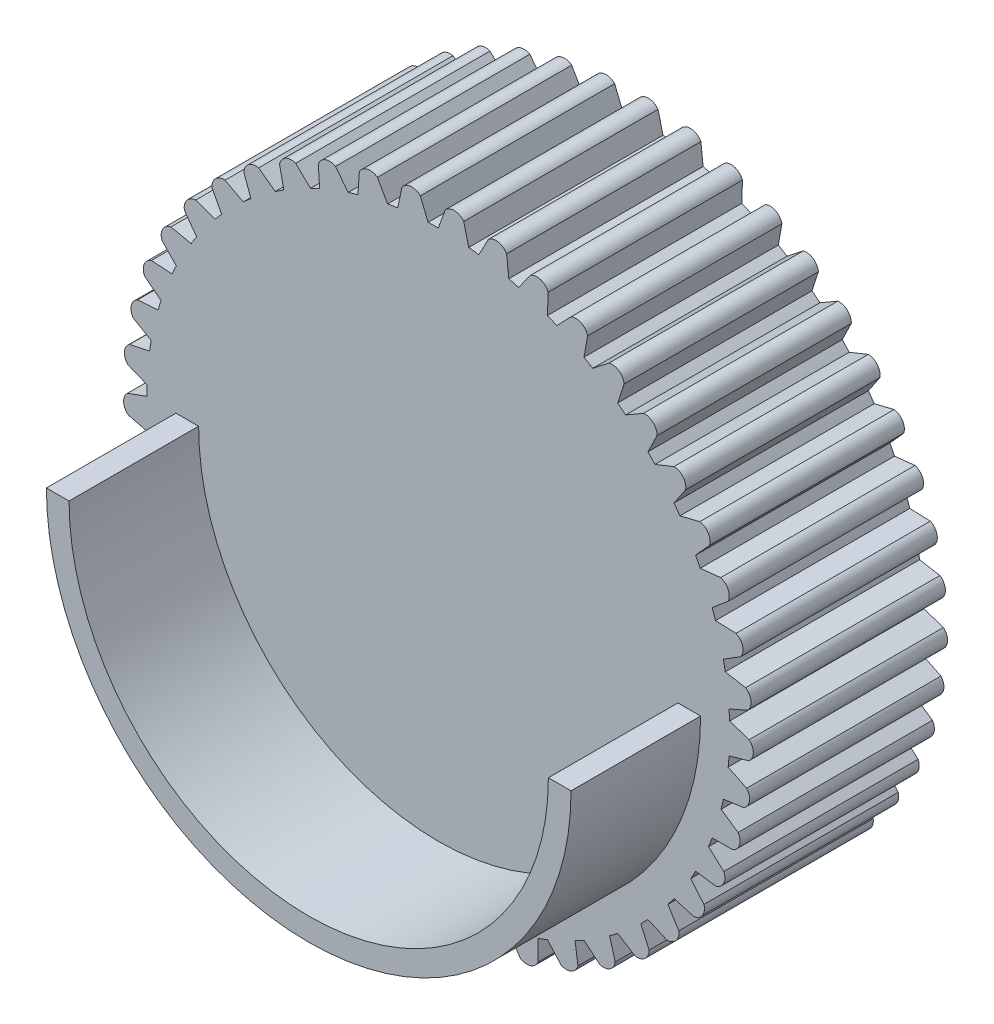
SolidWorks part; units mm, degrees
ref_plane "Front Plane" through (0, 0, 0) normal (0, 0, 1) x (1, 0, 0)
ref_plane "Top Plane" through (0, 0, 0) normal (0, 1, 0) x (1, 0, 0)
ref_plane "Right Plane" through (0, 0, 0) normal (1, 0, 0) x (0, 0, -1)
sketch "Sketch1" plane through (0, 0, 0) normal (0, 0, 1) x (1, 0, 0)
  circle A0 centre (0, 0) radius 22.5
  dimension "D1" = 45
extrude "Boss-Extrude1" add sketch "Sketch1" along normal blind 15
sketch "Sketch2" plane through (0, 0, 15) normal (0, 0, 1) x (1, 0, 0)
  circle A0 centre (0, 0) radius 20.25
  circle A1 centre (0, 0) radius 18.5
  dimension "D1" = 40.5
  dimension "D2" = 37
extrude "Boss-Extrude2" add sketch "Sketch2" along normal blind 10
sketch "Sketch3" plane through (0, 0, 15) normal (0, 0, 1) x (1, 0, 0)
  line L0 (0, 22.5) -> (0.5437, 23.9938)
  line L2 (2.3519, 22.3767) -> (1.9673, 23.9192)
  line L3 (0, 0) -> (0, 22.5)
  line L4 (2.3519, 22.3767) -> (0, 0)
  line L5 (0.5437, 23.9938) -> (1.9673, 23.9192)
  line L6 (0, 22.5) -> (0.5437, 23.9938)
  line L7 (1.9673, 23.9192) -> (2.3519, 22.3767)
  line L8 (3.1314, 22.281) -> (3.8777, 23.6847)
  line L9 (3.8777, 23.6847) -> (5.2771, 23.4127)
  line L10 (5.4432, 21.8317) -> (5.2771, 23.4127)
  line L11 (6.2018, 21.6284) -> (7.1362, 22.9145)
  line L12 (7.1362, 22.9145) -> (8.4841, 22.4504)
  line L13 (8.4286, 20.8616) -> (8.4841, 22.4504)
  line L14 (9.1516, 20.5548) -> (10.2559, 21.6983)
  line L15 (10.2559, 21.6983) -> (11.5261, 21.0511)
  line L16 (11.25, 19.4856) -> (11.5261, 21.0511)
  line L17 (11.9232, 19.0811) -> (13.1759, 20.0598)
  line L18 (13.1759, 20.0598) -> (14.3436, 19.2421)
  line L19 (13.8524, 17.7302) -> (14.3436, 19.2421)
  line L20 (14.4627, 17.236) -> (15.8395, 18.0309)
  line L21 (15.8395, 18.0309) -> (16.882, 17.0586)
  line L22 (16.1851, 15.6298) -> (16.882, 17.0586)
  line L23 (16.7208, 15.0554) -> (18.1947, 15.651)
  line L24 (18.1947, 15.651) -> (19.0918, 14.5431)
  line L25 (18.2029, 13.2252) -> (19.0918, 14.5431)
  line L26 (18.6533, 12.5818) -> (20.1958, 12.9664)
  line L27 (20.1958, 12.9664) -> (20.93, 11.7445)
  line L28 (19.8663, 10.5631) -> (20.93, 11.7445)
  line L29 (20.2229, 9.8634) -> (21.8039, 10.0295)
  line L30 (21.8039, 10.0295) -> (22.3609, 8.7173)
  line L31 (21.1431, 7.6955) -> (22.3609, 8.7173)
  line L32 (21.3988, 6.9529) -> (22.9875, 6.8974)
  line L33 (22.9875, 6.8974) -> (23.3565, 5.5204)
  line L34 (22.0083, 4.678) -> (23.3565, 5.5204)
  line L35 (22.1582, 3.9071) -> (23.7237, 3.631)
  line L36 (23.7237, 3.631) -> (23.8975, 2.2161)
  line L37 (22.4452, 1.5695) -> (23.8975, 2.2161)
  line L38 (22.4863, 0.7852) -> (23.9982, 0.294)
  line L39 (23.9982, 0.294) -> (23.9733, -1.1313)
  line L40 (22.4452, -1.5695) -> (23.9733, -1.1313)
  line L41 (22.3767, -2.3519) -> (23.8056, -3.0488)
  line L42 (23.8056, -3.0488) -> (23.5826, -4.4568)
  line L43 (22.0083, -4.678) -> (23.5826, -4.4568)
  line L44 (21.8317, -5.4432) -> (23.1496, -6.3322)
  line L45 (23.1496, -6.3322) -> (22.7328, -7.6955)
  line L46 (21.1431, -7.6955) -> (22.7328, -7.6955)
  line L47 (20.8616, -8.4286) -> (22.043, -9.4924)
  line L48 (22.043, -9.4924) -> (21.4406, -10.7844)
  line L49 (19.8663, -10.5631) -> (21.4406, -10.7844)
  line L50 (19.4856, -11.25) -> (20.5074, -12.4678)
  line L51 (20.5074, -12.4678) -> (19.731, -13.6634)
  line L52 (18.2029, -13.2252) -> (19.731, -13.6634)
  line L53 (17.7302, -13.8524) -> (18.5727, -15.2005)
  line L54 (18.5727, -15.2005) -> (17.6374, -16.2764)
  line L55 (16.1851, -15.6298) -> (17.6374, -16.2764)
  line L56 (15.6298, -16.1851) -> (16.2764, -17.6374)
  line L57 (16.2764, -17.6374) -> (15.2005, -18.5727)
  line L58 (13.8524, -17.7302) -> (15.2005, -18.5727)
  line L59 (13.2252, -18.2029) -> (13.6634, -19.731)
  line L60 (13.6634, -19.731) -> (12.4678, -20.5074)
  line L61 (11.25, -19.4856) -> (12.4678, -20.5074)
  line L62 (10.5631, -19.8663) -> (10.7844, -21.4406)
  line L63 (10.7844, -21.4406) -> (9.4924, -22.043)
  line L64 (8.4286, -20.8616) -> (9.4924, -22.043)
  line L65 (7.6955, -21.1431) -> (7.6955, -22.7328)
  line L66 (7.6955, -22.7328) -> (6.3322, -23.1496)
  line L67 (5.4432, -21.8317) -> (6.3322, -23.1496)
  line L68 (4.678, -22.0083) -> (4.4568, -23.5826)
  line L69 (4.4568, -23.5826) -> (3.0488, -23.8056)
  line L70 (2.3519, -22.3767) -> (3.0488, -23.8056)
  line L71 (1.5695, -22.4452) -> (1.1313, -23.9733)
  line L72 (1.1313, -23.9733) -> (-0.294, -23.9982)
  line L73 (-0.7852, -22.4863) -> (-0.294, -23.9982)
  line L74 (-1.5695, -22.4452) -> (-2.2161, -23.8975)
  line L75 (-2.2161, -23.8975) -> (-3.631, -23.7237)
  line L76 (-3.9071, -22.1582) -> (-3.631, -23.7237)
  line L77 (-4.678, -22.0083) -> (-5.5204, -23.3565)
  line L78 (-5.5204, -23.3565) -> (-6.8974, -22.9875)
  line L79 (-6.9529, -21.3988) -> (-6.8974, -22.9875)
  line L80 (-7.6955, -21.1431) -> (-8.7173, -22.3609)
  line L81 (-8.7173, -22.3609) -> (-10.0295, -21.8039)
  line L82 (-9.8634, -20.2229) -> (-10.0295, -21.8039)
  line L83 (-10.5631, -19.8663) -> (-11.7445, -20.93)
  line L84 (-11.7445, -20.93) -> (-12.9664, -20.1958)
  line L85 (-12.5818, -18.6533) -> (-12.9664, -20.1958)
  line L86 (-13.2252, -18.2029) -> (-14.5431, -19.0918)
  line L87 (-14.5431, -19.0918) -> (-15.651, -18.1947)
  line L88 (-15.0554, -16.7208) -> (-15.651, -18.1947)
  line L89 (-15.6298, -16.1851) -> (-17.0586, -16.882)
  line L90 (-17.0586, -16.882) -> (-18.0309, -15.8395)
  line L91 (-17.236, -14.4627) -> (-18.0309, -15.8395)
  line L92 (-17.7302, -13.8524) -> (-19.2421, -14.3436)
  line L93 (-19.2421, -14.3436) -> (-20.0598, -13.1759)
  line L94 (-19.0811, -11.9232) -> (-20.0598, -13.1759)
  line L95 (-19.4856, -11.25) -> (-21.0511, -11.5261)
  line L96 (-21.0511, -11.5261) -> (-21.6983, -10.2559)
  line L97 (-20.5548, -9.1516) -> (-21.6983, -10.2559)
  line L98 (-20.8616, -8.4286) -> (-22.4504, -8.4841)
  line L99 (-22.4504, -8.4841) -> (-22.9145, -7.1362)
  line L100 (-21.6284, -6.2018) -> (-22.9145, -7.1362)
  line L101 (-21.8317, -5.4432) -> (-23.4127, -5.2771)
  line L102 (-23.4127, -5.2771) -> (-23.6847, -3.8777)
  line L103 (-22.281, -3.1314) -> (-23.6847, -3.8777)
  line L104 (-22.3767, -2.3519) -> (-23.9192, -1.9673)
  line L105 (-23.9192, -1.9673) -> (-23.9938, -0.5437)
  line L106 (-22.5, 0) -> (-23.9938, -0.5437)
  line L107 (-22.4863, 0.7852) -> (-23.9602, 1.3808)
  line L108 (-23.9602, 1.3808) -> (-23.836, 2.8009)
  line L109 (-22.281, 3.1314) -> (-23.836, 2.8009)
  line L110 (-22.1582, 3.9071) -> (-23.5349, 4.7019)
  line L111 (-23.5349, 4.7019) -> (-23.2142, 6.0909)
  line L112 (-21.6284, 6.2018) -> (-23.2142, 6.0909)
  line L113 (-21.3988, 6.9529) -> (-22.6515, 7.9316)
  line L114 (-22.6515, 7.9316) -> (-22.1406, 9.2625)
  line L115 (-20.5548, 9.1516) -> (-22.1406, 9.2625)
  line L116 (-20.2229, 9.8634) -> (-21.3272, 11.0069)
  line L117 (-21.3272, 11.0069) -> (-20.6361, 12.2537)
  line L118 (-19.0811, 11.9232) -> (-20.6361, 12.2537)
  line L119 (-18.6533, 12.5818) -> (-19.5878, 13.8679)
  line L120 (-19.5878, 13.8679) -> (-18.7298, 15.0064)
  line L121 (-17.236, 14.4627) -> (-18.7298, 15.0064)
  line L122 (-16.7208, 15.0554) -> (-17.4671, 16.4591)
  line L123 (-17.4671, 16.4591) -> (-16.4591, 17.4671)
  line L124 (-15.0554, 16.7208) -> (-16.4591, 17.4671)
  line L125 (-14.4627, 17.236) -> (-15.0064, 18.7298)
  line L126 (-15.0064, 18.7298) -> (-13.8679, 19.5878)
  line L127 (-12.5818, 18.6533) -> (-13.8679, 19.5878)
  line L128 (-11.9232, 19.0811) -> (-12.2537, 20.6361)
  line L129 (-12.2537, 20.6361) -> (-11.0069, 21.3272)
  line L130 (-9.8634, 20.2229) -> (-11.0069, 21.3272)
  line L131 (-9.1516, 20.5548) -> (-9.2625, 22.1406)
  line L132 (-9.2625, 22.1406) -> (-7.9316, 22.6515)
  line L133 (-6.9529, 21.3988) -> (-7.9316, 22.6515)
  line L134 (-6.2018, 21.6284) -> (-6.0909, 23.2142)
  line L135 (-6.0909, 23.2142) -> (-4.7019, 23.5349)
  line L136 (-3.9071, 22.1582) -> (-4.7019, 23.5349)
  line L137 (-3.1314, 22.281) -> (-2.8009, 23.836)
  line L138 (-2.8009, 23.836) -> (-1.3808, 23.9602)
  line L139 (-0.7852, 22.4863) -> (-1.3808, 23.9602)
  arc A0 (0, 22.5) -> (2.3519, 22.3767) centre (0, 0) cw
  circle A1 centre (0, 0) radius 22.5 construction
  circle A2 centre (0, 0) radius 18.5 construction
  arc A4 (0.5437, 23.9938) -> (1.9673, 23.9192) centre (1.2243, 23.3613) cw
  arc A5 (0, 22.5) -> (2.3519, 22.3767) centre (0, 0) cw
  arc A6 (3.1314, 22.281) -> (5.4432, 21.8317) centre (0, 0) cw
  arc A7 (3.8777, 23.6847) -> (5.2771, 23.4127) centre (4.4637, 22.9636) cw
  arc A8 (6.2018, 21.6284) -> (8.4286, 20.8616) centre (0, 0) cw
  arc A9 (7.1362, 22.9145) -> (8.4841, 22.4504) centre (7.6161, 22.1189) cw
  arc A10 (9.1516, 20.5548) -> (11.25, 19.4856) centre (0, 0) cw
  arc A11 (10.2559, 21.6983) -> (11.5261, 21.0511) centre (10.6204, 20.8437) cw
  arc A12 (11.9232, 19.0811) -> (13.8524, 17.7302) centre (0, 0) cw
  arc A13 (13.1759, 20.0598) -> (14.3436, 19.2421) centre (13.4179, 19.1628) cw
  arc A14 (14.4627, 17.236) -> (16.1851, 15.6298) centre (0, 0) cw
  arc A15 (15.8395, 18.0309) -> (16.882, 17.0586) centre (15.9543, 17.1089) cw
  arc A16 (16.7208, 15.0554) -> (18.2029, 13.2252) centre (0, 0) cw
  arc A17 (18.1947, 15.651) -> (19.0918, 14.5431) centre (18.1801, 14.7219) cw
  arc A18 (18.6533, 12.5818) -> (19.8663, 10.5631) centre (0, 0) cw
  arc A19 (20.1958, 12.9664) -> (20.93, 11.7445) centre (20.0521, 12.0485) cw
  arc A20 (20.2229, 9.8634) -> (21.1431, 7.6955) centre (0, 0) cw
  arc A21 (21.8039, 10.0295) -> (22.3609, 8.7173) centre (21.5337, 9.1405) cw
  arc A22 (21.3988, 6.9529) -> (22.0083, 4.678) centre (0, 0) cw
  arc A23 (22.9875, 6.8974) -> (23.3565, 5.5204) centre (22.5963, 6.0547) cw
  arc A24 (22.1582, 3.9071) -> (22.4452, 1.5695) centre (0, 0) cw
  arc A25 (23.7237, 3.631) -> (23.8975, 2.2161) centre (23.219, 2.8509) cw
  arc A26 (22.4863, 0.7852) -> (22.4452, -1.5695) centre (0, 0) cw
  arc A27 (23.9982, 0.294) -> (23.9733, -1.1313) centre (23.3898, -0.4083) cw
  arc A28 (22.3767, -2.3519) -> (22.0083, -4.678) centre (0, 0) cw
  arc A29 (23.8056, -3.0488) -> (23.5826, -4.4568) centre (23.1054, -3.6595) cw
  arc A30 (21.8317, -5.4432) -> (21.1431, -7.6955) centre (0, 0) cw
  arc A31 (23.1496, -6.3322) -> (22.7328, -7.6955) centre (22.3712, -6.8396) cw
  arc A32 (20.8616, -8.4286) -> (19.8663, -10.5631) centre (0, 0) cw
  arc A33 (22.043, -9.4924) -> (21.4406, -10.7844) centre (21.2016, -9.8865) cw
  arc A34 (19.4856, -11.25) -> (18.2029, -13.2252) centre (0, 0) cw
  arc A35 (20.5074, -12.4678) -> (19.731, -13.6634) centre (19.6194, -12.741) cw
  arc A36 (17.7302, -13.8524) -> (16.1851, -15.6298) centre (0, 0) cw
  arc A37 (18.5727, -15.2005) -> (17.6374, -16.2764) centre (17.6552, -15.3475) cw
  arc A38 (15.6298, -16.1851) -> (13.8524, -17.7302) centre (0, 0) cw
  arc A39 (16.2764, -17.6374) -> (15.2005, -18.5727) centre (15.3475, -17.6552) cw
  arc A40 (13.2252, -18.2029) -> (11.25, -19.4856) centre (0, 0) cw
  arc A41 (13.6634, -19.731) -> (12.4678, -20.5074) centre (12.741, -19.6194) cw
  arc A42 (10.5631, -19.8663) -> (8.4286, -20.8616) centre (0, 0) cw
  arc A43 (10.7844, -21.4406) -> (9.4924, -22.043) centre (9.8865, -21.2016) cw
  arc A44 (7.6955, -21.1431) -> (5.4432, -21.8317) centre (0, 0) cw
  arc A45 (7.6955, -22.7328) -> (6.3322, -23.1496) centre (6.8396, -22.3712) cw
  arc A46 (4.678, -22.0083) -> (2.3519, -22.3767) centre (0, 0) cw
  arc A47 (4.4568, -23.5826) -> (3.0488, -23.8056) centre (3.6595, -23.1054) cw
  arc A48 (1.5695, -22.4452) -> (-0.7852, -22.4863) centre (0, 0) cw
  arc A49 (1.1313, -23.9733) -> (-0.294, -23.9982) centre (0.4083, -23.3898) cw
  arc A50 (-1.5695, -22.4452) -> (-3.9071, -22.1582) centre (0, 0) cw
  arc A51 (-2.2161, -23.8975) -> (-3.631, -23.7237) centre (-2.8509, -23.219) cw
  arc A52 (-4.678, -22.0083) -> (-6.9529, -21.3988) centre (0, 0) cw
  arc A53 (-5.5204, -23.3565) -> (-6.8974, -22.9875) centre (-6.0547, -22.5963) cw
  arc A54 (-7.6955, -21.1431) -> (-9.8634, -20.2229) centre (0, 0) cw
  arc A55 (-8.7173, -22.3609) -> (-10.0295, -21.8039) centre (-9.1405, -21.5337) cw
  arc A56 (-10.5631, -19.8663) -> (-12.5818, -18.6533) centre (0, 0) cw
  arc A57 (-11.7445, -20.93) -> (-12.9664, -20.1958) centre (-12.0485, -20.0521) cw
  arc A58 (-13.2252, -18.2029) -> (-15.0554, -16.7208) centre (0, 0) cw
  arc A59 (-14.5431, -19.0918) -> (-15.651, -18.1947) centre (-14.7219, -18.1801) cw
  arc A60 (-15.6298, -16.1851) -> (-17.236, -14.4627) centre (0, 0) cw
  arc A61 (-17.0586, -16.882) -> (-18.0309, -15.8395) centre (-17.1089, -15.9543) cw
  arc A62 (-17.7302, -13.8524) -> (-19.0811, -11.9232) centre (0, 0) cw
  arc A63 (-19.2421, -14.3436) -> (-20.0598, -13.1759) centre (-19.1628, -13.4179) cw
  arc A64 (-19.4856, -11.25) -> (-20.5548, -9.1516) centre (0, 0) cw
  arc A65 (-21.0511, -11.5261) -> (-21.6983, -10.2559) centre (-20.8437, -10.6204) cw
  arc A66 (-20.8616, -8.4286) -> (-21.6284, -6.2018) centre (0, 0) cw
  arc A67 (-22.4504, -8.4841) -> (-22.9145, -7.1362) centre (-22.1189, -7.6161) cw
  arc A68 (-21.8317, -5.4432) -> (-22.281, -3.1314) centre (0, 0) cw
  arc A69 (-23.4127, -5.2771) -> (-23.6847, -3.8777) centre (-22.9636, -4.4637) cw
  arc A70 (-22.3767, -2.3519) -> (-22.5, 0) centre (0, 0) cw
  arc A71 (-23.9192, -1.9673) -> (-23.9938, -0.5437) centre (-23.3613, -1.2243) cw
  arc A72 (-22.4863, 0.7852) -> (-22.281, 3.1314) centre (0, 0) cw
  arc A73 (-23.9602, 1.3808) -> (-23.836, 2.8009) centre (-23.3044, 2.0389) cw
  arc A74 (-22.1582, 3.9071) -> (-21.6284, 6.2018) centre (0, 0) cw
  arc A75 (-23.5349, 4.7019) -> (-23.2142, 6.0909) centre (-22.7938, 5.2624) cw
  arc A76 (-21.3988, 6.9529) -> (-20.5548, 9.1516) centre (0, 0) cw
  arc A77 (-22.6515, 7.9316) -> (-22.1406, 9.2625) centre (-21.8396, 8.3834) cw
  arc A78 (-20.2229, 9.8634) -> (-19.0811, 11.9232) centre (0, 0) cw
  arc A79 (-21.3272, 11.0069) -> (-20.6361, 12.2537) centre (-20.4603, 11.3413) cw
  arc A80 (-18.6533, 12.5818) -> (-17.236, 14.4627) centre (0, 0) cw
  arc A81 (-19.5878, 13.8679) -> (-18.7298, 15.0064) centre (-18.6828, 14.0785) cw
  arc A82 (-16.7208, 15.0554) -> (-15.0554, 16.7208) centre (0, 0) cw
  arc A83 (-17.4671, 16.4591) -> (-16.4591, 17.4671) centre (-16.5416, 16.5416) cw
  arc A84 (-14.4627, 17.236) -> (-12.5818, 18.6533) centre (0, 0) cw
  arc A85 (-15.0064, 18.7298) -> (-13.8679, 19.5878) centre (-14.0785, 18.6828) cw
  arc A86 (-11.9232, 19.0811) -> (-9.8634, 20.2229) centre (0, 0) cw
  arc A87 (-12.2537, 20.6361) -> (-11.0069, 21.3272) centre (-11.3413, 20.4603) cw
  arc A88 (-9.1516, 20.5548) -> (-6.9529, 21.3988) centre (0, 0) cw
  arc A89 (-9.2625, 22.1406) -> (-7.9316, 22.6515) centre (-8.3834, 21.8396) cw
  arc A90 (-6.2018, 21.6284) -> (-3.9071, 22.1582) centre (0, 0) cw
  arc A91 (-6.0909, 23.2142) -> (-4.7019, 23.5349) centre (-5.2624, 22.7938) cw
  arc A92 (-3.1314, 22.281) -> (-0.7852, 22.4863) centre (0, 0) cw
  arc A93 (-2.8009, 23.836) -> (-1.3808, 23.9602) centre (-2.0389, 23.3044) cw
  point P234 (0, 0)
  circle M9 centre (0, 0) radius 22.5
  dimension "D1" = 20
  dimension "D4" = 45
  dimension "D2" = 6
  dimension "D3" = 160
extrude "Boss-Extrude3" add sketch "Sketch3" against normal up to surface (15 mm away) contours L5 L0 L2 M9 | A4 L5 | L10 L9 L8 M9 | A7 L9 | L139 L138 L137 M9 | A93 L138 | L13 L12 L11 M9 | A9 L12 | L16 L15 L14 M9 | A11 L15 | L19 L18 L17 M9 | A13 L18 | L136 L135 L134 M9 | A91 L135 | L133 L132 L131 M9 | A89 L132 | L130 L129 L128 M9 | A87 L129 | L22 L21 L20 M9 | A15 L21 | L25 L24 L23 M9 | A17 L24 | L28 L27 L26 M9 | A19 L27 | L31 L30 L29 M9 | A21 L30 | L34 L33 L32 M9 | A23 L33 | L37 L36 L35 M9 | A25 L36 | L40 L39 L38 M9 | A27 L39 | L43 L42 L41 M9 | A29 L42 | L46 L45 L44 M9 | A31 L45 | L49 L48 L47 M9 | A33 L48 | L52 L51 L50 M9 | A35 L51 | L55 L54 L53 M9 | A37 L54 | L58 L57 L56 M9 | A39 L57 | L61 L60 L59 M9 | A41 L60 | L64 L63 L62 M9 | A43 L63 | L67 L66 L65 M9 | A45 L66 | L70 L69 L68 M9 | A47 L69 | L73 L72 L71 M9 | A49 L72 | L76 L75 L74 M9 | A51 L75 | L79 L78 L77 M9 | A53 L78 | L82 L81 L80 M9 | A55 L81 | L85 L84 L83 M9 | A57 L84 | L88 L87 L86 M9 | A59 L87 | L91 L90 L89 M9 | A61 L90 | L94 L93 L92 M9 | A63 L93 | L97 L96 L95 M9 | A65 L96 | L100 L99 L98 M9 | A67 L99 | L103 L102 L101 M9 | A69 L102 | L106 L105 L104 M9 | A71 L105 | L109 L108 L107 M9 | A73 L108 | L112 L111 L110 M9 | A75 L111 | L115 L114 L113 M9 | A77 L114 | L118 L117 L116 M9 | A79 L117 | L121 L120 L119 M9 | A81 L120 | L124 L123 L122 M9 | A83 L123 | L127 L126 L125 M9 | A85 L126 region at (1.2131, 23.147, 15) region at (1.2626, 24.0919, 15) region at (-2.0202, 23.0905, 15) region at (4.4227, 22.7529, 15) region at (-2.1026, 24.0331, 15) region at (4.6033, 23.6817, 15) region at (-5.2141, 22.5847, 15) region at (7.5463, 21.9159, 15) region at (-5.4269, 23.5066, 15) region at (7.8543, 22.8106, 15) region at (-8.3065, 21.6392, 15) region at (10.5229, 20.6524, 15) region at (-8.6456, 22.5226, 15) region at (10.9525, 21.4955, 15) region at (-11.2373, 20.2726, 15) region at (13.2948, 18.9869, 15) region at (-11.696, 21.1002, 15) region at (13.8375, 19.762, 15) region at (-13.9493, 18.5114, 15) region at (15.8079, 16.9519, 15) region at (-14.5188, 19.267, 15) region at (16.4532, 17.6439, 15) region at (-16.3898, 16.3898, 15) region at (18.0133, 14.5869, 15) region at (-17.0589, 17.0589, 15) region at (18.7486, 15.1823, 15) region at (-18.5114, 13.9493, 15) region at (19.8681, 11.9379, 15) region at (-19.267, 14.5188, 15) region at (20.6791, 12.4253, 15) region at (-20.2726, 11.2373, 15) region at (21.3361, 9.0567, 15) region at (-21.1002, 11.696, 15) region at (22.2071, 9.4264, 15) region at (-21.6392, 8.3065, 15) region at (22.3889, 5.9991, 15) region at (-22.5226, 8.6456, 15) region at (23.3029, 6.244, 15) region at (-22.5847, 5.2141, 15) region at (23.006, 2.8248, 15) region at (-23.5066, 5.4269, 15) region at (23.9451, 2.9401, 15) region at (-23.0905, 2.0202, 15) region at (23.1752, -0.4045, 15) region at (-24.0331, 2.1026, 15) region at (24.1213, -0.421, 15) region at (-23.147, -1.2131, 15) region at (-24.0919, -1.2626, 15) region at (22.8934, -3.626, 15) region at (-22.7529, -4.4227, 15) region at (23.8279, -3.774, 15) region at (-23.6817, -4.6033, 15) region at (22.1659, -6.7768, 15) region at (-21.9159, -7.5463, 15) region at (23.0708, -7.0535, 15) region at (-22.8106, -7.8543, 15) region at (21.0071, -9.7958, 15) region at (-20.6524, -10.5229, 15) region at (21.8646, -10.1956, 15) region at (-21.4955, -10.9525, 15)
sketch "Sketch4" plane through (0, 0, 0) normal (1, 0, 0) x (0, 0, -1)
  line L0 (-25, 20.25) -> (-25, -20.25) construction
  line L1 (-25, 0) -> (-15, 0)
  line L2 (-25, 0) -> (-25, 24.7521)
  line L3 (-25, 24.7521) -> (-15, 24.7521)
  line L4 (-15, 0) -> (-15, 24.7521)
extrude "Cut-Extrude1" cut sketch "Sketch4" against normal through all both and the other way through all
